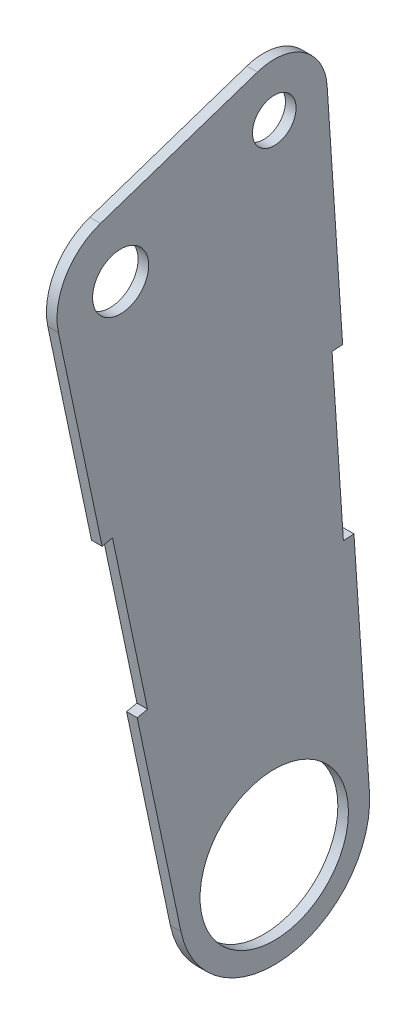
SolidWorks part; units mm, degrees
material "AISI 4130 Steel, annealed at 865C"
ref_plane "X-Y Datum" through (0, 0, 0) normal (0, 0, 1) x (1, 0, 0)
ref_plane "X-Z Datum" through (0, 0, 0) normal (0, 1, 0) x (1, 0, 0)
ref_plane "Y-Z Datum" through (0, 0, 0) normal (1, 0, 0) x (0, 0, -1)
sketch "Sketch1" plane through (0, 0, 0) normal (1, 0, 0) x (0, 0, -1)
  line L0 (0, 0) -> (-23.009, 85.8708) construction
  line L1 (0, 0) -> (0, 95.25) construction
  line L2 (-32.3283, 83.902) -> (-13.9789, -2.9532)
  line L3 (7.9198, 95.7792) -> (14.2557, 0.9525)
  line L4 (-26.0336, 94.9028) -> (-2.5205, 102.7767)
  line L5 (-20.5285, 28.0486) -> (-25.7787, 52.9001)
  line L6 (-20.5285, 28.0486) -> (-18.9753, 28.3768)
  line L7 (-25.7787, 52.9001) -> (-24.2255, 53.2282)
  line L8 (-18.9753, 28.3768) -> (-24.2255, 53.2282)
  line L9 (-20.5285, 28.0486) -> (-24.2255, 53.2282) construction
  line L10 (-25.7787, 52.9001) -> (-18.9753, 28.3768) construction
  line L11 (-22.805, 94.3099) -> (-4.7409, 100.359)
  line L12 (-22.805, 94.3099) -> (-23.3091, 95.8152)
  line L13 (-4.7409, 100.359) -> (-5.245, 101.8643)
  line L14 (-23.3091, 95.8152) -> (-5.245, 101.8643)
  line L15 (-22.805, 94.3099) -> (-5.245, 101.8643) construction
  line L16 (-4.7409, 100.359) -> (-23.3091, 95.8152) construction
  line L17 (10.3524, 35.56) -> (8.6553, 60.96)
  line L18 (10.3524, 35.56) -> (11.9363, 35.6658)
  line L19 (8.6553, 60.96) -> (10.2392, 61.0658)
  line L20 (11.9363, 35.6658) -> (10.2392, 61.0658)
  line L21 (10.3524, 35.56) -> (10.2392, 61.0658) construction
  line L22 (8.6553, 60.96) -> (11.9363, 35.6658) construction
  arc A0 (-13.9789, -2.9532) -> (14.2557, 0.9525) centre (0, 0) ccw
  arc A1 (-32.3283, 83.902) -> (-26.0336, 94.9028) centre (-23.009, 85.8708) cw
  arc A2 (-2.5205, 102.7767) -> (7.9198, 95.7792) centre (0, 95.25) cw
  circle A3 centre (0, 0) radius 11.1125
  circle A4 centre (0, 0) radius 11.1125 construction
  circle A5 centre (0, 0) radius 14.2875 construction
  point P1 (-23.1536, 40.4744)
  point P12 (-22.377, 40.6384)
  point P14 (21.1318, 6.4606)
  point P16 (-23.1536, 40.4744)
  point P18 (-14.277, 98.8398)
  point P26 (-14.025, 98.0871)
  point P27 (-14.277, 98.8398)
  point P28 (11.0878, 48.3658)
  point P33 (11.0878, 48.3658)
  point P34 (10.2958, 48.3129)
  dimension "D2" = 7.9375
  dimension "D7" = 9.525
  dimension "D3" = 1.5875
  dimension "D4" = 25.4
  dimension "D5" = 19.05
  dimension "D6" = 25.4
  dimension "D1" = 3.175
extrude "Boss-Extrude1" add sketch "Sketch1" along normal blind 1.5875 contours A2 L4 L13 L11 L12 A1 L2 L7 L8 L6 A0 L3 L18 L17 L19 A3 region at (0, 52.637, 6.9643)
hole_wizard "1/4 Clearance Hole1" positions "Sketch2" profile "Sketch3" hole size "1/4" standard "ANSI Inch" end condition through all
sketch "Sketch2" plane through (1.5875, 0, 0) normal (1, 0, 0) x (0, 0, -1)
  point P2 (0, 95.25)
sketch "Sketch3" plane through (1.5875, 95.25, 0) normal (0, 1, 0) x (0, 0, -1)
  line L0 (0, 0) -> (0, 1.5875)
  line L1 (0, 1.5875) -> (3.2639, 1.5875)
  line L2 (3.2639, 1.5875) -> (3.2639, 0)
  line L5 (3.2639, 0) -> (0, 0)
  line L11 (0, -6.35) -> (0, 107.95) construction
  dimension "Thru Hole Dia." = 6.5278
  dimension "Thru Hole Depth" = 1.5875
hole_wizard "M8 Clearance Hole1" positions "Sketch4" profile "Sketch5" hole size "M8" standard "ANSI Metric" end condition through all
sketch "Sketch4" plane through (1.5875, 0, 0) normal (1, 0, 0) x (0, 0, -1)
  point P0 (-23.009, 85.8708)
sketch "Sketch5" plane through (1.5875, 85.8708, 23.009) normal (0, 1, 0) x (0, 0, -1)
  line L0 (0, 0) -> (0, 1.5875)
  line L1 (0, 1.5875) -> (4.2, 1.5875)
  line L2 (4.2, 1.5875) -> (4.2, 0)
  line L5 (4.2, 0) -> (0, 0)
  line L11 (0, -6.35) -> (0, 107.95) construction
  dimension "Thru Hole Dia." = 8.4
  dimension "Thru Hole Depth" = 1.5875
extrude "Boss-Extrude2" add sketch "Sketch1<3>" along normal up to surface (1.5875 mm away) contours L11 L13 L4 L12 region at (0, 98.0871, 14.025) up to face at (1.5875, 85.8708, 18.809)
sketch "Sketch1<3>" plane through (0, 0, 0) normal (1, 0, 0) x (0, 0, -1) same geometry as "Sketch1"
